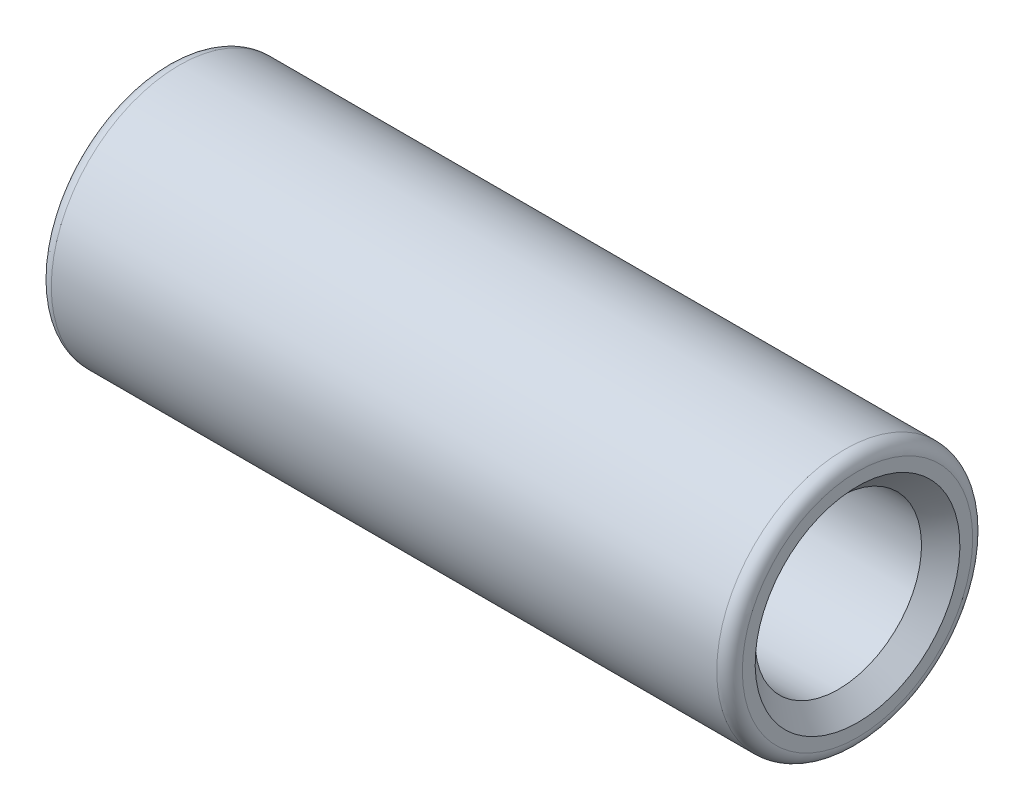
SolidWorks part; units mm, degrees
ref_plane "Front" through (0, 0, 0) normal (0, 0, 1) x (1, 0, 0)
ref_plane "Top" through (0, 0, 0) normal (0, 1, 0) x (1, 0, 0)
ref_plane "Right" through (0, 0, 0) normal (1, 0, 0) x (0, 0, -1)
sketch "Sketch1" plane through (0, 0, 0) normal (0, 0, 1) x (1, 0, 0)
  line L0 (0, 0) -> (36, 0) construction
  line L1 (25, 4.05) -> (0, 4.05)
  line L4 (54, 10) -> (54, 6.5)
  line L5 (54, 6.5) -> (30, 6.5)
  line L6 (30, 6.5) -> (30, 2.775)
  line L7 (30, 2.775) -> (36, 2.775)
  line L8 (36, 2.775) -> (36, 0)
  line L9 (36, 0) -> (25, 0)
  line L10 (25, 0) -> (25, 4.05)
  line L11 (54, 10) -> (0, 10)
  line L14 (0, 10) -> (0, 4.05)
  dimension "D1" = 8.1
  dimension "D2" = 25
  dimension "D3" = 5.55
  dimension "D4" = 13
  dimension "D5" = 6
  dimension "D6" = 24
  dimension "D7" = 5
  dimension "D8" = 3.5
revolve "Revolve1" add sketch "Sketch1" angle 360 about L0
chamfer "Chamfer1" distance 1.5 angle 45 3 edges at (36, -2.775, 0) (54, -6.5, 0) (0, -4.05, 0)
fillet "Fillet1" radius 1 2 edges at (0, -10, 0) (54, -10, 0)
